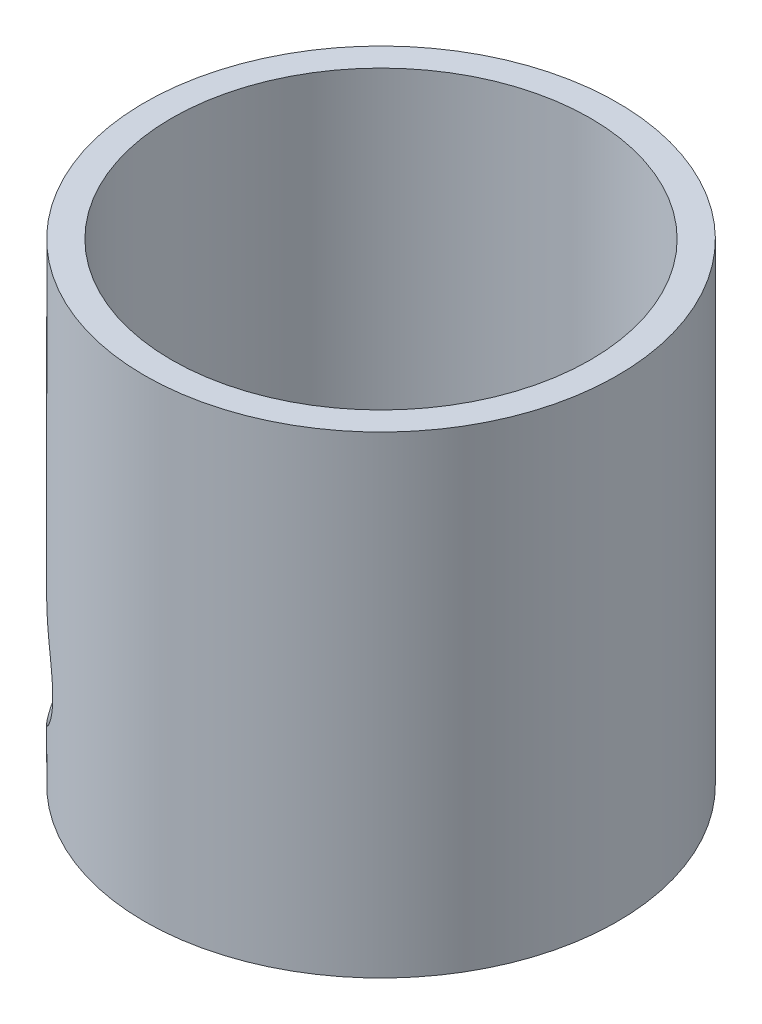
SolidWorks part; units mm, degrees
ref_plane "Front Plane" through (0, 0, 0) normal (0, 0, 1) x (1, 0, 0)
ref_plane "Top Plane" through (0, 0, 0) normal (0, 1, 0) x (1, 0, 0)
ref_plane "Right Plane" through (0, 0, 0) normal (1, 0, 0) x (0, 0, -1)
sketch "Sketch1" plane through (0, 0, 0) normal (0, 1, 0) x (1, 0, 0)
  line L0 (-20, 0) -> (20, 0) construction
  circle A0 centre (0, 0) radius 20
  dimension "D1" = 40
sketch "Sketch3" plane through (0, 0, 0) normal (0, 1, 0) x (1, 0, 0)
  circle A0 centre (0, 0) radius 87.5
  circle A1 centre (0, 0) radius 77.5
  dimension "D1" = 175
  dimension "D2" = 10
extrude "Boss-Extrude1" add sketch "Sketch3" along normal blind 175 separate body
extrude "Boss-Extrude2" add sketch "Sketch3<2>" along normal blind 5 contours A1 region at (0, 0, 0)
sketch "Sketch3<2>" plane through (0, 0, 0) normal (0, 1, 0) x (1, 0, 0) same geometry as "Sketch3"
sketch "Sketch4" plane through (0, 0, 0) normal (1, 0, 0) x (0, 0, -1)
  line L0 (77.5, 0) -> (-77.5, 0) construction
  circle A0 centre (-47.5, 40) radius 25
  point P2 (-77.5, 0)
  point P5 (-80.1126, 0)
  point P7 (-77.5, 0)
  point P8 (-53.3723, 32.6467)
  dimension "D1" = 50
  dimension "D2" = 30
  dimension "D3" = 40
extrude "Cut-Extrude1" cut sketch "Sketch4" against normal through all
